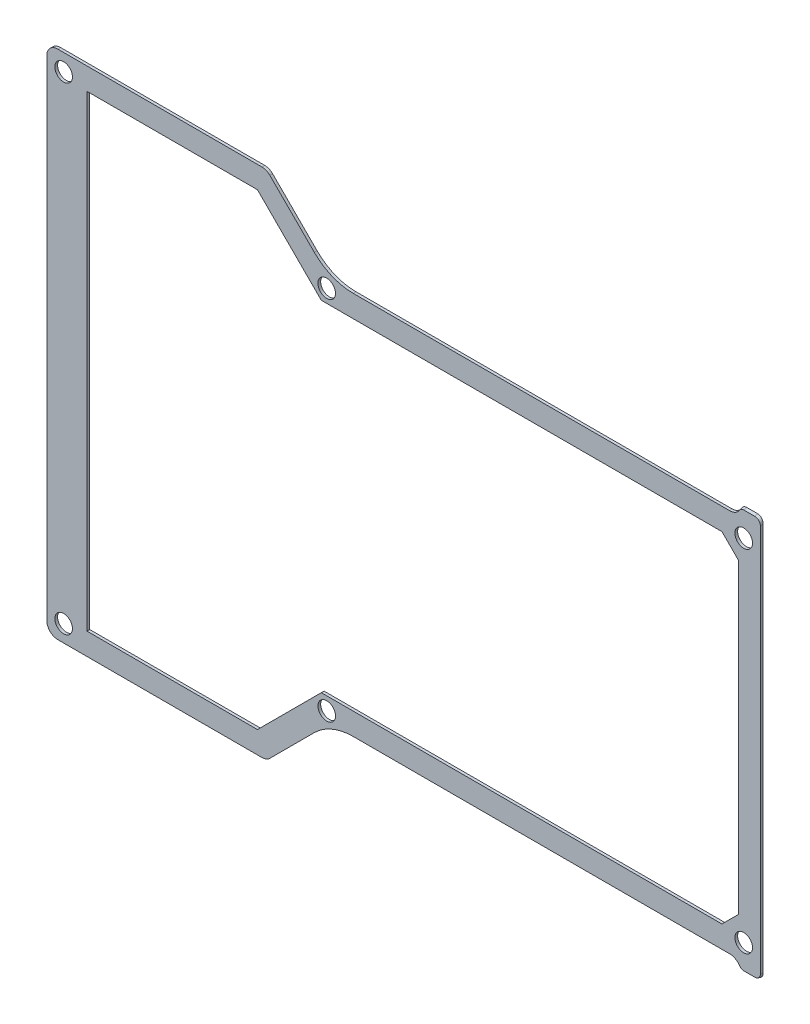
SolidWorks part; units mm, degrees
ref_plane "Front Plane" through (0, 0, 0) normal (0, 0, 1) x (1, 0, 0)
ref_plane "Top Plane" through (0, 0, 0) normal (0, 1, 0) x (1, 0, 0)
ref_plane "Right Plane" through (0, 0, 0) normal (1, 0, 0) x (0, 0, -1)
sketch "Sketch1" plane through (0, 0, 0) normal (0, 0, 1) x (1, 0, 0)
  line L0 (20, -100.2696) -> (0, -100.2696) construction
  line L1 (31.61, -88.6596) -> (20, -100.2696) construction
  line L2 (104.455, -88.6596) -> (31.61, -88.6596) construction
  line L3 (104.455, -88.6596) -> (107.455, -85.6596) construction
  line L4 (107.455, -29.8746) -> (107.455, -85.6596) construction
  line L5 (104.455, -26.8746) -> (107.455, -29.8746) construction
  line L6 (31.605, -26.8746) -> (104.455, -26.8746) construction
  line L7 (20, -15.2696) -> (31.605, -26.8746) construction
  line L8 (0, -100.2696) -> (0, -15.2696) construction
  line L9 (0, -15.2696) -> (20, -15.2696) construction
  line L10 (30.3329, -19.9457) -> (22.2426, -11.8554) construction
  line L11 (107.455, -22.8746) -> (37.404, -22.8746) construction
  line L12 (108.455, -21.3054) -> (110.455, -21.3054) construction
  line L15 (37.409, -92.6596) -> (107.455, -92.6596) construction
  line L16 (22.2426, -103.6838) -> (30.3379, -95.5885) construction
  line L17 (-16.3, -104.2696) -> (20.8284, -104.2696) construction
  line L18 (-18.3, -13.2696) -> (-18.3, -102.2696) construction
  line L19 (20.8284, -11.2696) -> (-16.3, -11.2696) construction
  line L20 (20, -100.2696) -> (0, -100.2696)
  line L21 (31.61, -88.6596) -> (20, -100.2696)
  line L22 (104.455, -88.6596) -> (31.61, -88.6596)
  line L23 (104.455, -88.6596) -> (107.455, -85.6596)
  line L24 (107.455, -29.8746) -> (107.455, -85.6596)
  line L25 (104.455, -26.8746) -> (107.455, -29.8746)
  line L26 (31.605, -26.8746) -> (104.455, -26.8746)
  line L27 (20, -15.2696) -> (31.605, -26.8746)
  line L28 (0, -100.2696) -> (0, -15.2696)
  line L29 (0, -15.2696) -> (20, -15.2696)
  line L30 (30.3329, -19.9457) -> (22.2426, -11.8554)
  line L31 (107.455, -22.8746) -> (37.404, -22.8746)
  line L32 (108.455, -21.3054) -> (110.455, -21.3054)
  line L33 (107.455, -94.2295) -> (111.455, -94.2295)
  line L34 (111.455, -94.2295) -> (111.455, -21.3054)
  line L35 (37.409, -92.6596) -> (107.455, -92.6596)
  line L36 (22.2426, -103.6838) -> (30.3379, -95.5885)
  line L37 (-16.3, -104.2696) -> (20.8284, -104.2696)
  line L38 (-18.3, -13.2696) -> (-18.3, -102.2696)
  line L39 (20.8284, -11.2696) -> (-16.3, -11.2696)
  line L40 (111.455, -21.3054) -> (107.455, -21.3054)
  line L41 (107.455, -94.2295) -> (107.455, -92.6596)
  line L42 (107.455, -21.3054) -> (107.455, -22.8746)
  arc A0 (22.2426, -11.8554) -> (20.8284, -11.2696) centre (20.8284, -13.2696) ccw construction
  arc A1 (30.3329, -19.9457) -> (37.404, -22.8746) centre (37.404, -12.8746) ccw construction
  arc A2 (37.409, -92.6596) -> (30.3379, -95.5885) centre (37.409, -102.6596) ccw construction
  arc A3 (20.8284, -104.2696) -> (22.2426, -103.6838) centre (20.8284, -102.2696) ccw construction
  arc A4 (-18.3, -102.2696) -> (-16.3, -104.2696) centre (-16.3, -102.2696) ccw construction
  arc A5 (-16.3, -11.2696) -> (-18.3, -13.2696) centre (-16.3, -13.2696) ccw construction
  arc A6 (22.2426, -11.8554) -> (20.8284, -11.2696) centre (20.8284, -13.2696) ccw
  arc A7 (30.3329, -19.9457) -> (37.404, -22.8746) centre (37.404, -12.8746) ccw
  arc A8 (37.409, -92.6596) -> (30.3379, -95.5885) centre (37.409, -102.6596) ccw
  arc A9 (20.8284, -104.2696) -> (22.2426, -103.6838) centre (20.8284, -102.2696) ccw
  arc A10 (-18.3, -102.2696) -> (-16.3, -104.2696) centre (-16.3, -102.2696) ccw
  arc A11 (-16.3, -11.2696) -> (-18.3, -13.2696) centre (-16.3, -13.2696) ccw
  circle A12 centre (108.4121, -25.9175) radius 1.25 construction
  circle A13 centre (32.5911, -24.494) radius 1.25 construction
  circle A14 centre (-15.2393, -14.3303) radius 1.25 construction
  circle A15 centre (-15.2393, -101.2089) radius 1.25 construction
  circle A16 centre (32.5961, -91.0402) radius 1.25 construction
  circle A17 centre (108.4121, -89.6167) radius 1.25 construction
  circle A18 centre (108.4121, -25.9175) radius 1.25 construction
  circle A19 centre (32.5911, -24.494) radius 1.25 construction
  circle A20 centre (-15.2393, -14.3303) radius 1.25 construction
  circle A21 centre (-15.2393, -101.2089) radius 1.25 construction
  circle A22 centre (32.5961, -91.0402) radius 1.25 construction
  circle A23 centre (108.4121, -89.6167) radius 1.25 construction
  circle A24 centre (-15.2393, -101.2089) radius 1.6
  circle A25 centre (32.5961, -91.0402) radius 1.6
  circle A26 centre (108.4121, -89.6167) radius 1.6
  circle A27 centre (108.4121, -25.9175) radius 1.6
  circle A28 centre (32.5911, -24.494) radius 1.6
  circle A29 centre (-15.2393, -14.3303) radius 1.6
extrude "Boss-Extrude1" add sketch "Sketch1" along normal blind 0.5 contours L39 A11 L38 A10 L37 A9 L36 A8 L35 L41 L33 L34 L40 L32 L42 L31 A7 L30 A6 A29 A28 A27 A26 A25 A24 L28 L29 L27 L26 L25 L24 L23 L22 L21 L20 region at (33.5161, -22.2609, 0)
sketch "Sketch2" plane through (111.455, 0, 0) normal (1, 0, 0) x (0, 0, -1)
  line L2 (28.78, -11.2696) -> (0, -21.3054)
  line L3 (0, -94.2295) -> (28.78, -104.2696)
  line L4 (0, -21.3054) -> (-2.5092, -22.1804)
  line L5 (-2.5092, -22.1804) -> (-2.2343, -18.9333)
  line L6 (-2.2343, -18.9333) -> (1.8663, -18.9333)
  line L7 (1.8663, -18.9333) -> (0, -21.3054)
  line L8 (0, -94.2295) -> (-3.7144, -92.9337)
  line L9 (-3.7144, -92.9337) -> (-3.7144, -98.6628)
  line L10 (-3.7144, -98.6628) -> (4.2666, -98.6628)
  line L11 (4.2666, -98.6628) -> (0, -94.2295)
extrude "Cut-Extrude3" cut sketch "Sketch2" against normal blind 10 contours L10 L11 L8 L9 | L7 L6 L5 L4 | L4 | L8 region at (111.455, -20.2093, 0.7767) region at (111.455, -96.4678, 0.815)
fillet "Fillet1" radius 1 4 edges at (107.455, -94.1422, 0.25) (111.455, -94.1422, 0.25) (107.455, -21.3926, 0.25) (111.455, -21.3926, 0.25)
sketch "Sketch3" plane through (0, 0, 0.5) normal (0, 0, 1) x (1, 0, 0)
  line L0 (0, -100.2696) -> (0, -15.2696) construction
  line L2 (104.455, -88.6596) -> (31.61, -88.6596) construction
  line L3 (31.61, -88.6596) -> (20, -100.2696) construction
  line L5 (31.605, -26.8746) -> (104.455, -26.8746) construction
  line L6 (20, -15.2696) -> (31.605, -26.8746) construction
  line L7 (0, -100.2696) -> (0, -15.2696)
  line L8 (20, -100.2696) -> (31.61, -87.476)
  line L9 (104.455, -88.6596) -> (31.61, -88.6596)
  line L10 (31.61, -88.6596) -> (20, -100.2696)
  line L11 (31.61, -87.476) -> (104.455, -88.6596)
  line L12 (31.605, -26.8746) -> (104.455, -26.8746)
  line L13 (20, -15.2696) -> (31.605, -26.8746)
  line L14 (0, -15.2696) -> (-11, -15.2696)
  line L15 (-11, -15.2696) -> (-11, -100.2696)
  line L16 (-11, -100.2696) -> (0, -100.2696)
  line M29 (0, -100.2696) -> (0, -15.2696)
extrude "Cut-Extrude4" cut sketch "Sketch3" against normal blind 10 contours L15 L16 L14 M29 region at (-5.5, -57.7696, 0.5)
fillet "Fillet2" radius 2 2 edges at (107.455, -92.6596, 0.25) (107.455, -22.8746, 0.25)
